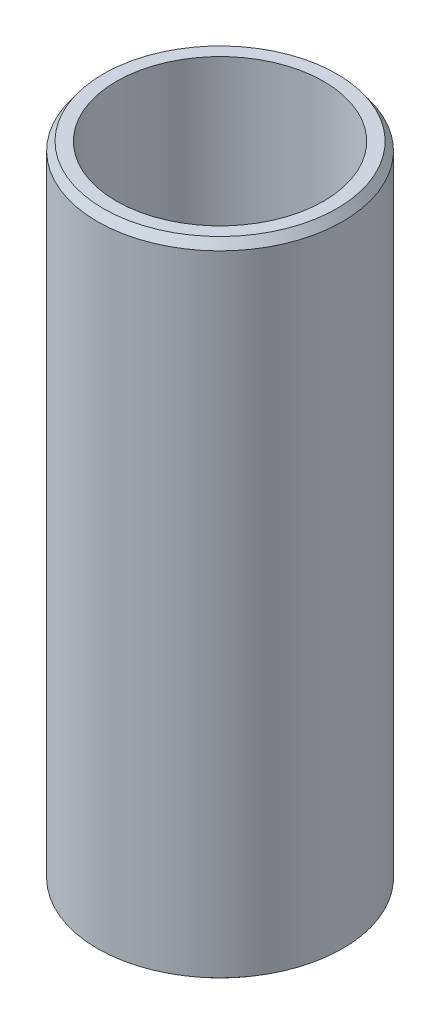
SolidWorks part; units mm, degrees
ref_plane "Front Plane" through (0, 0, 0) normal (0, 0, 1) x (1, 0, 0)
ref_plane "Top Plane" through (0, 0, 0) normal (0, 1, 0) x (1, 0, 0)
ref_plane "Right Plane" through (0, 0, 0) normal (1, 0, 0) x (0, 0, -1)
sketch "Sketch1" plane through (0, 0, 0) normal (0, 1, 0) x (1, 0, 0)
  circle A0 centre (0, 0) radius 57.5
  dimension "SHAFT_OD" = 115
extrude "Boss-Extrude1" add sketch "Sketch1" along normal blind 301.8354
sketch "Sketch2" plane through (0, 0, 0) normal (0, 1, 0) x (1, 0, 0)
  circle A0 centre (0, 0) radius 48.6317
  dimension "BORE_D" = 97.2634
extrude "Cut-Extrude1" cut sketch "Sketch2" along normal through all
chamfer "Chamfer1" distance 3.8754 angle 35.625 2 edges at (0, 301.8354, 57.5) (0, 0, 57.5) first distance on face at (0, 301.8354, 57.5) first distance on face at (0, 0, 48.6317)
